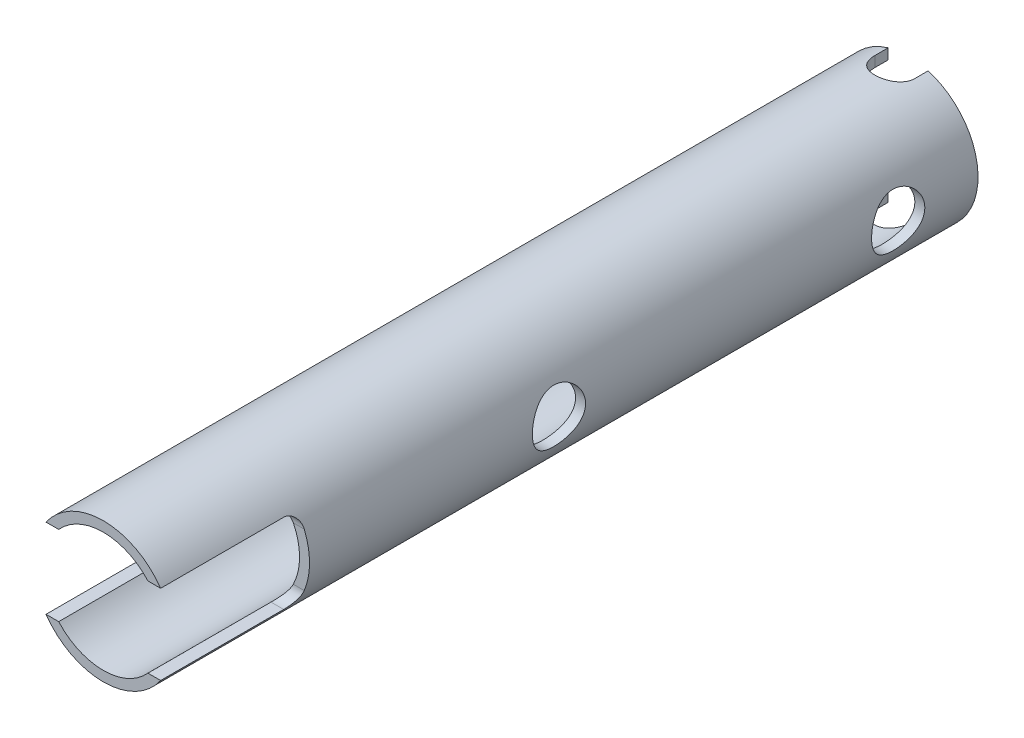
SolidWorks part; units mm, degrees
material "ABS"
ref_plane "前视基准面" through (0, 0, 0) normal (0, 0, 1) x (1, 0, 0)
ref_plane "上视基准面" through (0, 0, 0) normal (0, 1, 0) x (1, 0, 0)
ref_plane "右视基准面" through (0, 0, 0) normal (1, 0, 0) x (0, 0, -1)
sketch "草图1" plane through (0, 0, 0) normal (0, 0, 1) x (1, 0, 0)
  circle A0 centre (0, 0) radius 9
  circle A1 centre (0, 0) radius 10.5
  dimension "D1" = 18
  dimension "D2" = 21
extrude "凸台-拉伸1" add sketch "草图1" along normal blind 20 and the other way blind 118
sketch "草图2" plane through (0, 0, 0) normal (1, 0, 0) x (0, 0, -1)
  line L1 (-15.5, -6) -> (15.5, -6)
  line L2 (-17.5, -4) -> (-17.5, 4)
  line L3 (-15.5, 6) -> (15.5, 6)
  line L4 (17.5, -4) -> (17.5, 4)
  line L5 (-17.5, -6) -> (17.5, 6) construction
  line L6 (-17.5, 6) -> (17.5, -6) construction
  arc A0 (-15.5, -6) -> (-17.5, -4) centre (-15.5, -4) cw
  arc A1 (15.5, -6) -> (17.5, -4) centre (15.5, -4) ccw
  arc A2 (15.5, 6) -> (17.5, 4) centre (15.5, 4) cw
  arc A3 (-17.5, 4) -> (-15.5, 6) centre (-15.5, 4) cw
  point P0 (0, 0)
  dimension "D3" = 2
  dimension "D1" = 35
  dimension "D2" = 12
extrude "切除-拉伸1" cut sketch "草图2" against normal through all and the other way through all
ref_plane "基准面1" through (0, 0, 10.6) normal (0, 0, 1) x (1, 0, 0)
sketch "草图3" plane through (0, 0, 10.6) normal (0, 0, 1) x (1, 0, 0)
  line L0 (0, 0) -> (6.9214, -11.9883) construction
  line L1 (3.7319, -6.4638) -> (5.4639, -5.4638)
  line L2 (5.4639, -5.4638) -> (8.3059, -10.3863)
  line L3 (8.3059, -10.3863) -> (6.5739, -11.3863)
  line L4 (3.7319, -6.4638) -> (6.5739, -11.3863)
  line L5 (0, 0) -> (0, -9) construction
  circle A0 centre (0, 0) radius 9 construction
  dimension "D1" = 4
  dimension "D2" = 30
revolve "切除-旋转1" [suppressed] cut sketch "草图3" angle 360 about L0
mirror "镜向1" [suppressed] about plane through (0, 0, 0) normal (1, 0, 0)
sketch "草图4" plane through (0, 0, 0) normal (0, 1, 0) x (1, 0, 0)
  line L1 (-0.1, -6.5) -> (0.1, -6.5)
  line L2 (-1.1, -7.5) -> (-1.1, -12.5)
  line L3 (-0.1, -13.5) -> (0.1, -13.5)
  line L4 (1.1, -7.5) -> (1.1, -12.5)
  line L5 (-1.1, -6.5) -> (1.1, -13.5) construction
  line L6 (-1.1, -13.5) -> (1.1, -6.5) construction
  arc A0 (-0.1, -6.5) -> (-1.1, -7.5) centre (-0.1, -7.5) ccw
  arc A1 (0.1, -6.5) -> (1.1, -7.5) centre (0.1, -7.5) cw
  arc A2 (0.1, -13.5) -> (1.1, -12.5) centre (0.1, -12.5) ccw
  arc A3 (-1.1, -12.5) -> (-0.1, -13.5) centre (-0.1, -12.5) ccw
  point P0 (0, -10)
  dimension "D4" = 1
  dimension "D1" = 2.2
  dimension "D2" = 13.5
  dimension "D3" = 7
extrude "切除-拉伸2" [suppressed] cut sketch "草图4" against normal blind 20
sketch "草图5" plane through (0, 0, 0) normal (0, 1, 0) x (1, 0, 0)
  line L0 (0, 118) -> (0, 116) construction
  line L1 (10.5, 118) -> (-10.5, 118) construction
  line L2 (3, 116) -> (3, 118)
  line L3 (-3, 116) -> (-3, 118)
  line L4 (3, 118) -> (-3, 118)
  arc A0 (-3, 116) -> (3, 116) centre (0, 116) ccw
  dimension "D1" = 2
  dimension "D2" = 6
extrude "切除-拉伸3" cut sketch "草图5" along normal blind 20 and the other way through all
sketch "草图6" plane through (0, 0, 0) normal (1, 0, 0) x (0, 0, -1)
  line L0 (118, -10.0623) -> (118, 10.0623) construction
  circle A0 centre (106, 0) radius 4
  circle A1 centre (55, 0) radius 4
  dimension "D1" = 12
  dimension "D2" = 51
  dimension "D3" = 8
extrude "切除-拉伸4" cut sketch "草图6" along normal blind 20 and the other way blind 20
sketch "草图8" plane through (0, 0, 0) normal (0, 1, 0) x (1, 0, 0)
  line L0 (4.5, -16) -> (-4.5, -16)
  line L1 (5.5, -17) -> (5.5, -24)
  line L2 (-5.5, -17) -> (-5.5, -24)
  line L3 (5.5, -24) -> (-5.5, -24)
  line L4 (5.5, -16) -> (-5.5, -24) construction
  line L5 (-5.5, -16) -> (5.5, -24) construction
  line L6 (-10.5, -20) -> (10.5, -20) construction
  arc A0 (5.5, -17) -> (4.5, -16) centre (4.5, -17) ccw
  arc A1 (-4.5, -16) -> (-5.5, -17) centre (-4.5, -17) ccw
  point P1 (0, -20)
  dimension "D3" = 1
  dimension "D1" = 11
  dimension "D2" = 4
extrude "切除-拉伸5" cut sketch "草图8" against normal blind 33 and the other way blind 33
fillet "圆角1" radius 1 4 edges at (5.5, -8.0341, 20) (-5.5, -8.0341, 20) (5.5, 8.0341, 20) (-5.5, 8.0341, 20)
sketch "草图9" plane through (0, 0, 10.6) normal (0, 0, 1) x (1, 0, 0)
  line L0 (0, 0) -> (0, -7.9012) construction
  line L3 (-6.5, -3.2763) -> (6.5, -3.2763)
  line L4 (-6.5, -3.2763) -> (-6.5, -11.1477)
  line L5 (-6.5, -11.1477) -> (6.5, -11.1477)
  line L6 (6.5, -3.2763) -> (6.5, -11.1477)
  dimension "D1" = 6.5
extrude "切除-拉伸6" [suppressed] cut sketch "草图9" against normal blind 5 and the other way blind 2
fillet "圆角2" [suppressed] radius 1
ref_plane "基准面2" through (0, 0, 3) normal (0, 0, 1) x (1, 0, 0)
sketch "草图10" plane through (0, 0, 3) normal (0, 0, 1) x (1, 0, 0)
  line L1 (-13.3424, 14.286) -> (13.3424, 14.286)
  line L2 (-13.3424, 14.286) -> (-13.3424, -6)
  line L3 (-13.3424, -6) -> (13.3424, -6)
  line L4 (13.3424, 14.286) -> (13.3424, -6)
  line L5 (-13.3424, 14.286) -> (13.3424, -6) construction
  line L6 (-13.3424, -6) -> (13.3424, 14.286) construction
  point P0 (0, 4.143)
  dimension "D1" = 6
extrude "切除-拉伸7" cut sketch "草图10" along normal blind 17
sketch "草图11" plane through (0, 0, 3) normal (0, 0, 1) x (1, 0, 0)
  circle A0 centre (0, 0) radius 13.8227
extrude "切除-拉伸8" cut sketch "草图11" along normal through all
